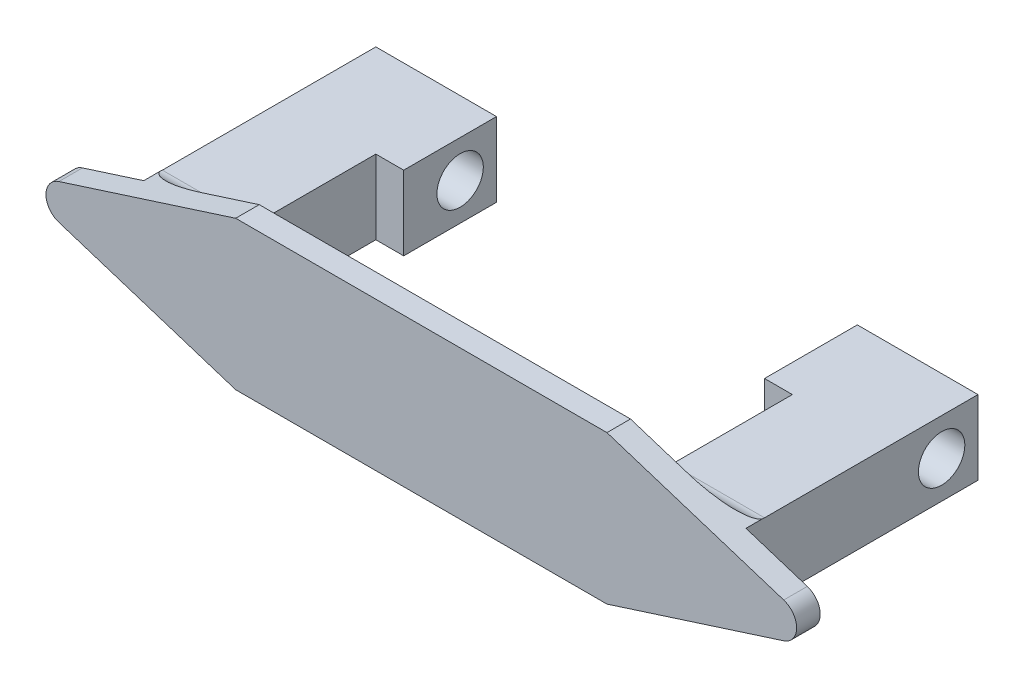
SolidWorks part; units mm, degrees
ref_plane "Front Plane" through (0, 0, 0) normal (0, 0, 1) x (1, 0, 0)
ref_plane "Top Plane" through (0, 0, 0) normal (0, 1, 0) x (1, 0, 0)
ref_plane "Right Plane" through (0, 0, 0) normal (1, 0, 0) x (0, 0, -1)
sketch "Sketch1" plane through (0, 0, 0) normal (0, 0, 1) x (1, 0, 0)
  line L0 (-45, 0) -> (-20, 8)
  line L1 (-20, 8) -> (20, 8)
  line L2 (0, 8) -> (0, 0) construction
  line L3 (-45, 0) -> (0, 0) construction
  line L4 (45, 0) -> (20, 8)
  line L5 (45, 0) -> (20, -8)
  line L6 (-20, -8) -> (20, -8)
  line L7 (-45, 0) -> (-20, -8)
  dimension "D1" = 45
  dimension "D2" = 8
  dimension "D3" = 20
extrude "Boss-Extrude1" add sketch "Sketch1" along normal mid plane 2.54
fillet "Fillet1" radius 2 2 edges at (45, 0, 0) (-45, 0, 0)
sketch "Sketch2" plane through (0, 0, 0) normal (0, 1, 0) x (1, 0, 0)
  line L0 (-32.4378, 1.27) -> (-32.4378, 26.27)
  line L2 (-32.4378, 1.27) -> (-22.4378, 1.27)
  line L3 (-32.4378, 26.27) -> (-19.4378, 26.27)
  line L5 (0, 0) -> (0, 26.27) construction
  line L6 (22.4378, 16.27) -> (22.4378, 1.27)
  line L7 (-19.4378, 26.27) -> (-19.4378, 16.27)
  line L8 (-19.4378, 16.27) -> (-22.4378, 16.27)
  line L9 (-22.4378, 16.27) -> (-22.4378, 1.27)
  line L10 (19.4378, 16.27) -> (22.4378, 16.27)
  line L11 (19.4378, 26.27) -> (19.4378, 16.27)
  line L12 (32.4378, 26.27) -> (19.4378, 26.27)
  line L13 (32.4378, 1.27) -> (22.4378, 1.27)
  line L14 (32.4378, 1.27) -> (32.4378, 26.27)
  line L15 (-20, 1.27) -> (-39.0473, 1.27) construction
  dimension "D1" = 25
  dimension "D2" = 10
  dimension "D3" = 8
  dimension "D4" = 13
extrude "Boss-Extrude2" add sketch "Sketch2" along normal mid plane 8
sketch "Sketch3" plane through (0, 0, 0) normal (1, 0, 0) x (0, 0, -1)
  circle A0 centre (22.3504, 0) radius 2.5
  dimension "D1" = 5
extrude "Cut-Extrude1" cut sketch "Sketch3" against normal through all both and the other way through all
fillet "Fillet2" radius 2 6 edges at (27.4378, -4, -1.27) (22.4378, 0, -1.27) (27.4378, 4, -1.27) (-27.4378, -4, -1.27) (-27.4378, 4, -1.27) (-22.4378, 0, -1.27)
